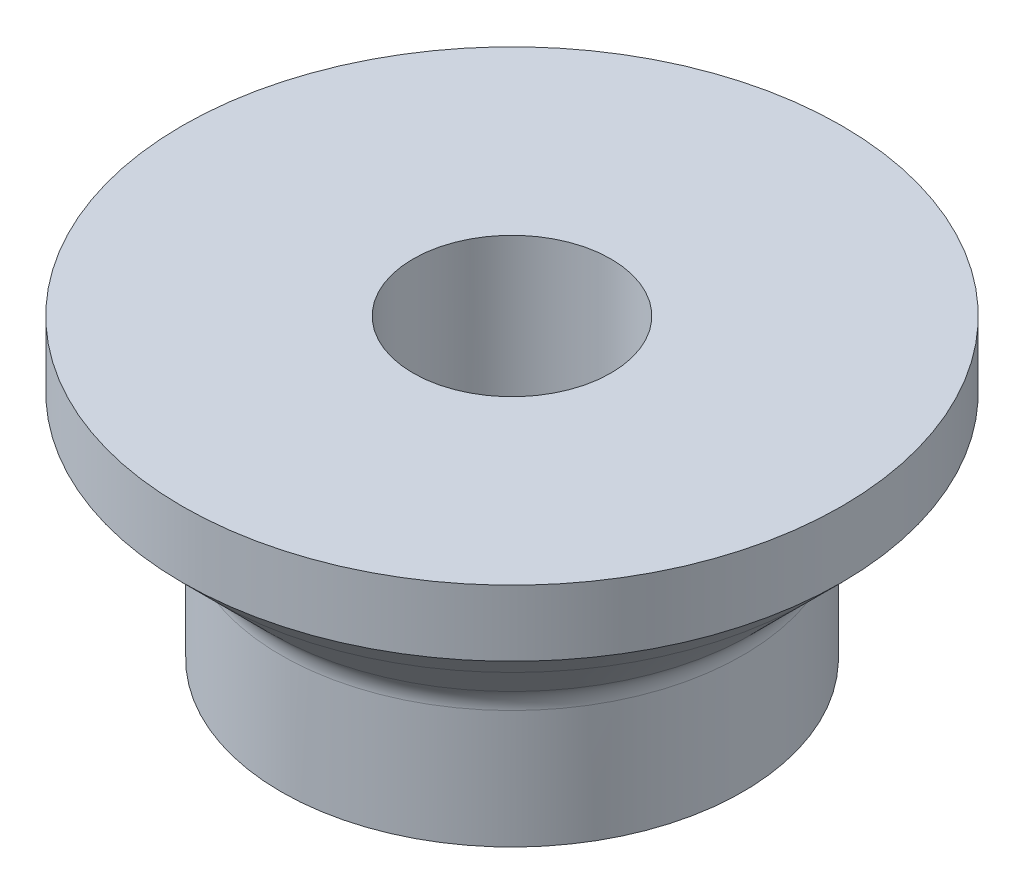
SolidWorks part; units mm, degrees
ref_plane "Front Plane" through (0, 0, 0) normal (0, 0, 1) x (1, 0, 0)
ref_plane "Top Plane" through (0, 0, 0) normal (0, 1, 0) x (1, 0, 0)
ref_plane "Right Plane" through (0, 0, 0) normal (1, 0, 0) x (0, 0, -1)
sketch "Sketch1" plane through (0, 0, 0) normal (0, 1, 0) x (1, 0, 0)
  circle A0 centre (0, 0) radius 7
  circle A1 centre (0, 0) radius 3
  dimension "D1" = 6
  dimension "D2" = 14
extrude "Boss-Extrude1" add sketch "Sketch1" along normal blind 9
sketch "Sketch2" plane through (0, 9, 0) normal (0, 1, 0) x (1, 0, 0)
  circle A0 centre (0, 0) radius 10
  circle A1 centre (0, 0) radius 3
  circle A2 centre (0, 0) radius 3 construction
  dimension "D1" = 20
extrude "Boss-Extrude2" add sketch "Sketch2" against normal blind 3
sketch "Sketch3" plane through (0, 0, 0) normal (0, -1, 0) x (1, 0, 0)
  line L1 (-4.0017, -2.8407) -> (0.4593, -4.8859)
  line L2 (0.4593, -4.8859) -> (4.461, -2.0452)
  line L3 (4.461, -2.0452) -> (4.0017, 2.8407)
  line L4 (4.0017, 2.8407) -> (-0.4593, 4.8859)
  line L5 (-0.4593, 4.8859) -> (-4.461, 2.0452)
  line L6 (-4.461, 2.0452) -> (-4.0017, -2.8407)
  circle A0 centre (0, 0) radius 4.25 construction
  dimension "D1" = 8.5
extrude "Cut-Extrude1" cut sketch "Sketch3" against normal blind 3
chamfer "Chamfer1" distance 2 angle 45 1 edges at (0, 6, 7)
chamfer "Chamfer2" distance 1 angle 45 1 edges at (0, 6, 10)
fillet "Fillet1" radius 1 1 edges at (0, 4, 7)
